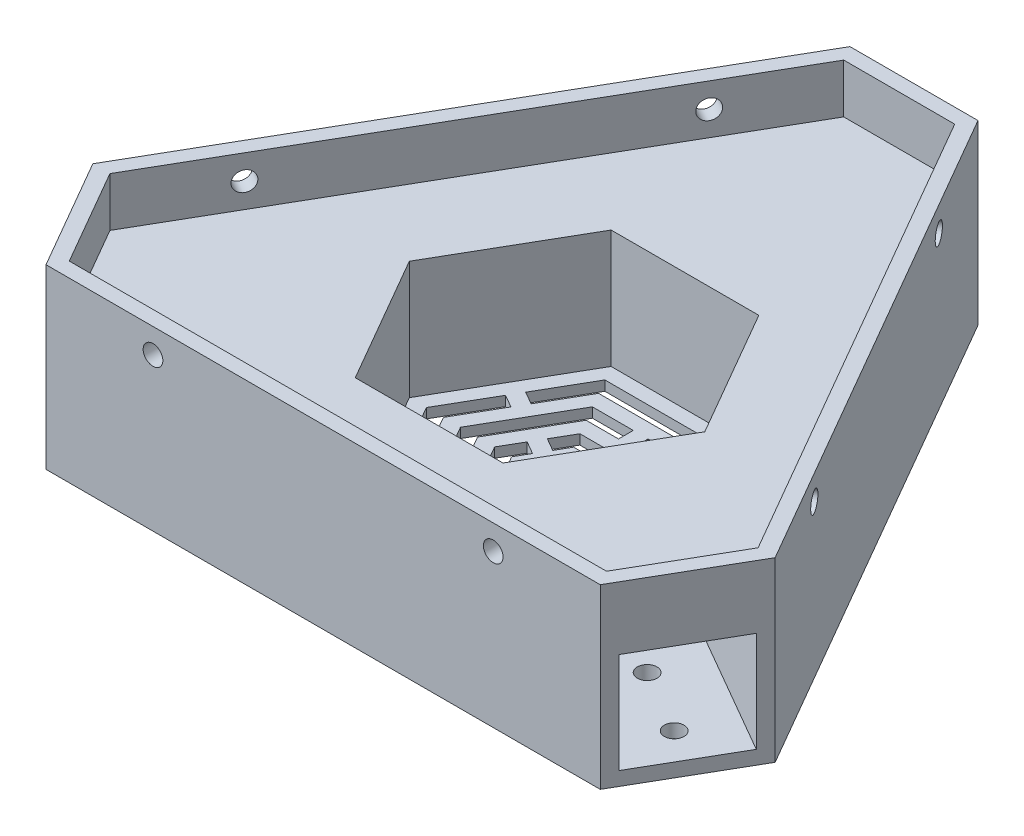
SolidWorks part; units mm, degrees
ref_plane "Front Plane" through (0, 0, 0) normal (0, 0, 1) x (1, 0, 0)
ref_plane "Top Plane" through (0, 0, 0) normal (0, 1, 0) x (1, 0, 0)
ref_plane "Right Plane" through (0, 0, 0) normal (1, 0, 0) x (0, 0, -1)
sketch "Sketch1" plane through (0, 0, 0) normal (0, 1, 0) x (1, 0, 0)
  line L0 (-11.2679, 69.4944) -> (11.2679, 69.4944)
  line L1 (15, 25.9808) -> (-15, 25.9808)
  line L2 (-15, 25.9808) -> (-30, 0)
  line L3 (-30, 0) -> (-15, -25.9808)
  line L4 (-15, -25.9808) -> (15, -25.9808)
  line L5 (15, -25.9808) -> (30, 0)
  line L6 (30, 0) -> (15, 25.9808)
  line L7 (-11.2679, 69.4944) -> (-38.5429, 22.2528)
  line L8 (11.2679, 69.4944) -> (38.5429, 22.2528)
  line L9 (41.141, 23.7528) -> (13, 72.4944)
  line L10 (13, 72.4944) -> (-13, 72.4944)
  line L11 (-13, 72.4944) -> (-41.141, 23.7528)
  line L12 (0, 0) -> (0, 113.4171) construction
  line L13 (0, 0) -> (-77.6761, 44.8463) construction
  line L14 (0, 0) -> (87.0373, 50.251) construction
  line L15 (69.282, -24.9889) -> (41.141, 23.7528)
  line L16 (65.8179, -24.9889) -> (38.5429, 22.2528)
  line L17 (56.282, -47.5056) -> (69.282, -24.9889)
  line L18 (65.8179, -24.9889) -> (54.55, -44.5056)
  line L19 (0, -47.5056) -> (56.282, -47.5056)
  line L20 (54.55, -44.5056) -> (0, -44.5056)
  line L21 (-56.282, -47.5056) -> (0, -47.5056)
  line L22 (-54.55, -44.5056) -> (0, -44.5056)
  line L23 (-69.282, -24.9889) -> (-56.282, -47.5056)
  line L24 (-54.55, -44.5056) -> (-65.8179, -24.9889)
  line L25 (-41.141, 23.7528) -> (-69.282, -24.9889)
  line L26 (-65.8179, -24.9889) -> (-38.5429, 22.2528)
  circle A0 centre (0, 0) radius 25.9808 construction
  point P15 (0, 69.4944)
  point P19 (0, 72.4944)
  point P41 (0, 0)
  dimension "D1" = 30
  dimension "D2" = 3
  dimension "D3" = 3
  dimension "D5" = 26
  dimension "D6" = 120
  dimension "D4" = 3
extrude "Boss-Extrude1" add sketch "Sketch1" along normal blind 2 contours L5 L6 L1 L2 L3 L4 region at (0, 0, 0)
extrude "Boss-Extrude2" add sketch "Sketch1<3>" along normal blind 26 contours L11 L25 L23 L21 L19 L17 L15 L9 L10 L24 L26 L7 L0 L8 L16 L18 L20 L22 | L26 L24 L22 L20 L18 L16 L8 L0 L7 L6 L5 L4 L3 L2 L1 region at (0, 0, -67.7531) region at (53.6241, 0, 1.5346)
sketch "Sketch1<3>" plane through (0, 0, 0) normal (0, 1, 0) x (1, 0, 0) same geometry as "Sketch1"
sketch "Sketch2" plane through (62.782, 0, 36.2472) normal (0.866, 0, 0.5) x (0.5, 0, -0.866)
  line L0 (-13, 26) -> (13, 0) construction
  line L1 (13, 26) -> (-13, 0) construction
  line L3 (-10.2, 2.8) -> (10.2, 2.8)
  line L4 (-10.2, 2.8) -> (-10.2, 23.2)
  line L5 (-10.2, 23.2) -> (10.2, 23.2)
  line L6 (10.2, 2.8) -> (10.2, 23.2)
  line L7 (-10.2, 2.8) -> (10.2, 23.2) construction
  line L8 (-10.2, 23.2) -> (10.2, 2.8) construction
  point P8 (0, 13)
  dimension "D1" = 20.4
extrude "Cut-Extrude1" cut sketch "Sketch2" against normal blind 30
ref_axis "Axis1" through (0, 27.3, 0) along (0, -1, 0)
pattern_circular "CirPattern1" count 3 over 360 about axis through (0, 27.3, 0) along (0, -1, 0) of "Cut-Extrude1"
sketch "Sketch3" plane through (0, 26, 0) normal (0, 1, 0) x (1, 0, 0)
  line L0 (-15, -25.9808) -> (15, -25.9808)
  line L1 (15, -25.9808) -> (30, 0)
  line L2 (30, 0) -> (15, 25.9808)
  line L3 (15, 25.9808) -> (-15, 25.9808)
  line L4 (-15, 25.9808) -> (-30, 0)
  line L5 (-30, 0) -> (-15, -25.9808)
  line L6 (0, -25.9808) -> (0, 25.9808) construction
  line L7 (1.5, 25.9808) -> (1.5, -25.9808) construction
  line L8 (-1.5, 25.9808) -> (-1.5, -25.9808) construction
  line L9 (23.25, -11.6913) -> (-21.75, 14.2894) construction
  line L10 (-22.5, 12.9904) -> (22.5, -12.9904) construction
  line L11 (21.75, -14.2894) -> (-23.25, 11.6913) construction
  line L12 (-21.75, -14.2894) -> (23.25, 11.6913) construction
  line L13 (22.5, 12.9904) -> (-22.5, -12.9904) construction
  line L14 (-23.25, -11.6913) -> (21.75, 14.2894) construction
  line L15 (30, 0) -> (15, 25.9808) construction
  line L16 (0, 22.9808) -> (13.2679, 22.9808)
  line L17 (13.2679, 22.9808) -> (19.1519, 12.7894)
  line L18 (19.1519, 12.7894) -> (16.5538, 11.2894)
  line L19 (16.5538, 11.2894) -> (11.5359, 19.9808)
  line L20 (11.5359, 19.9808) -> (0, 19.9808)
  line L21 (19.6077, 0) -> (9.8038, 16.9808)
  line L22 (9.8038, 16.9808) -> (1.5, 16.9808)
  line L23 (1.5, 16.9808) -> (1.5, 13.9808)
  line L24 (1.5, 13.9808) -> (8.0718, 13.9808)
  line L25 (8.0718, 13.9808) -> (16.1436, 0)
  line L26 (6.1615, 5.2894) -> (8.7596, 6.7894)
  line L27 (8.7596, 6.7894) -> (6.3397, 10.9808)
  line L28 (6.3397, 10.9808) -> (0, 10.9808)
  line L29 (8.7596, 6.7894) -> (10.2596, 4.1913)
  line L30 (6.1615, 5.2894) -> (7.6615, 2.6913)
  line L31 (6.1615, 5.2894) -> (4.6077, 7.9808)
  line L32 (4.6077, 7.9808) -> (1.5, 7.9808)
  line L33 (1.5, 7.9808) -> (0, 7.9808)
  line L34 (1.5, 7.9808) -> (1.5, 4.9808)
  line L35 (1.5, 4.9808) -> (2.8756, 4.9808)
  line L36 (2.8756, 4.9808) -> (5.7513, 0)
  line L37 (7.6615, -2.6913) -> (5.0635, -1.1913)
  line L38 (7.6615, 2.6913) -> (10.2596, 4.1913)
  line L39 (15.4558, -7.1913) -> (12.8577, -5.6913)
  line L40 (20.6519, 10.1913) -> (18.0538, 8.6913)
  line L41 (5.0635, -1.1913) -> (5.7513, 0)
  line L42 (7.6615, 2.6913) -> (9.2154, 0)
  line L43 (7.6615, -2.6913) -> (6.9115, -3.9904)
  line L44 (9.2154, 0) -> (7.6615, -2.6913)
  line L45 (10.2596, 4.1913) -> (12.6795, 0)
  line L46 (12.6795, 0) -> (9.5096, -5.4904)
  line L47 (12.8577, -5.6913) -> (16.1436, 0)
  line L48 (19.6077, 0) -> (15.4558, -7.1913)
  line L49 (18.0538, 8.6913) -> (23.0718, 0)
  line L50 (23.0718, 0) -> (17.3038, -9.9904)
  line L51 (26.5359, 0) -> (20.6519, 10.1913)
  line L52 (19.9019, -11.4904) -> (26.5359, 0)
  line L53 (19.9019, -11.4904) -> (13.2679, -22.9808)
  line L54 (13.2679, -22.9808) -> (1.5, -22.9808)
  line L55 (1.5, -22.9808) -> (1.5, -19.9808)
  line L56 (1.5, -19.9808) -> (11.5359, -19.9808)
  line L57 (11.5359, -19.9808) -> (17.3038, -9.9904)
  line L58 (-9.8038, -16.9808) -> (9.8038, -16.9808)
  line L59 (9.8038, -16.9808) -> (13.9558, -9.7894)
  line L60 (13.9558, -9.7894) -> (11.3577, -8.2894)
  line L61 (11.3577, -8.2894) -> (8.0718, -13.9808)
  line L62 (8.0718, -13.9808) -> (-8.0718, -13.9808)
  line L63 (1.5, -7.9808) -> (1.5, -10.9808)
  line L64 (1.5, -10.9808) -> (6.3397, -10.9808)
  line L65 (6.3397, -10.9808) -> (9.5096, -5.4904)
  line L66 (1.5, -10.9808) -> (-1.5, -10.9808)
  line L67 (1.5, -7.9808) -> (-1.5, -7.9808)
  line L68 (1.5, -7.9808) -> (4.6077, -7.9808)
  line L69 (4.6077, -7.9808) -> (6.1615, -5.2894)
  line L70 (6.1615, -5.2894) -> (6.9115, -3.9904)
  line L71 (6.1615, -5.2894) -> (3.5635, -3.7894)
  line L72 (3.5635, -3.7894) -> (2.8756, -4.9808)
  line L73 (2.8756, -4.9808) -> (-2.8756, -4.9808)
  line L74 (-6.1615, -5.2894) -> (-3.5635, -3.7894)
  line L75 (-1.5, -7.9808) -> (-1.5, -10.9808)
  line L76 (-13.9558, -9.7894) -> (-11.3577, -8.2894)
  line L77 (-1.5, -22.9808) -> (-1.5, -19.9808)
  line L78 (-3.5635, -3.7894) -> (-2.8756, -4.9808)
  line L79 (-1.5, -7.9808) -> (-4.6077, -7.9808)
  line L80 (-6.1615, -5.2894) -> (-6.9115, -3.9904)
  line L81 (-4.6077, -7.9808) -> (-6.1615, -5.2894)
  line L82 (-1.5, -10.9808) -> (-6.3397, -10.9808)
  line L83 (-6.3397, -10.9808) -> (-9.5096, -5.4904)
  line L84 (-11.3577, -8.2894) -> (-8.0718, -13.9808)
  line L85 (-9.8038, -16.9808) -> (-13.9558, -9.7894)
  line L86 (-1.5, -19.9808) -> (-11.5359, -19.9808)
  line L87 (-11.5359, -19.9808) -> (-17.3038, -9.9904)
  line L88 (-13.2679, -22.9808) -> (-1.5, -22.9808)
  line L89 (-19.9019, -11.4904) -> (-13.2679, -22.9808)
  line L90 (-19.9019, -11.4904) -> (-26.5359, 0)
  line L91 (-26.5359, 0) -> (-20.6519, 10.1913)
  line L92 (-20.6519, 10.1913) -> (-18.0538, 8.6913)
  line L93 (-18.0538, 8.6913) -> (-23.0718, 0)
  line L94 (-23.0718, 0) -> (-17.3038, -9.9904)
  line L95 (-9.8038, 16.9808) -> (-19.6077, 0)
  line L96 (-19.6077, 0) -> (-15.4558, -7.1913)
  line L97 (-15.4558, -7.1913) -> (-12.8577, -5.6913)
  line L98 (-12.8577, -5.6913) -> (-16.1436, 0)
  line L99 (-16.1436, 0) -> (-8.0718, 13.9808)
  line L100 (-7.6615, 2.6913) -> (-10.2596, 4.1913)
  line L101 (-10.2596, 4.1913) -> (-12.6795, 0)
  line L102 (-12.6795, 0) -> (-9.5096, -5.4904)
  line L103 (-10.2596, 4.1913) -> (-8.7596, 6.7894)
  line L104 (-7.6615, 2.6913) -> (-6.1615, 5.2894)
  line L105 (-7.6615, 2.6913) -> (-9.2154, 0)
  line L106 (-9.2154, 0) -> (-7.6615, -2.6913)
  line L107 (-7.6615, -2.6913) -> (-6.9115, -3.9904)
  line L108 (-7.6615, -2.6913) -> (-5.0635, -1.1913)
  line L109 (-5.0635, -1.1913) -> (-5.7513, 0)
  line L110 (-5.7513, 0) -> (-2.8756, 4.9808)
  line L111 (-1.5, 7.9808) -> (-1.5, 4.9808)
  line L112 (-6.1615, 5.2894) -> (-8.7596, 6.7894)
  line L113 (-1.5, 16.9808) -> (-1.5, 13.9808)
  line L114 (-19.1519, 12.7894) -> (-16.5538, 11.2894)
  line L115 (-1.5, 4.9808) -> (-2.8756, 4.9808)
  line L116 (-6.1615, 5.2894) -> (-4.6077, 7.9808)
  line L117 (-1.5, 7.9808) -> (0, 7.9808)
  line L118 (-4.6077, 7.9808) -> (-1.5, 7.9808)
  line L119 (-8.7596, 6.7894) -> (-6.3397, 10.9808)
  line L120 (-6.3397, 10.9808) -> (0, 10.9808)
  line L121 (-1.5, 13.9808) -> (-8.0718, 13.9808)
  line L122 (-9.8038, 16.9808) -> (-1.5, 16.9808)
  line L123 (-16.5538, 11.2894) -> (-11.5359, 19.9808)
  line L124 (-11.5359, 19.9808) -> (0, 19.9808)
  line L125 (-13.2679, 22.9808) -> (-19.1519, 12.7894)
  line L126 (0, 22.9808) -> (-13.2679, 22.9808)
  line L127 (-1.5, 4.9808) -> (1.5, 4.9808)
  line L128 (5.0635, -1.1913) -> (3.5635, -3.7894)
  line L129 (-5.0635, -1.1913) -> (-3.5635, -3.7894)
  line L130 (15, 25.9808) -> (0, 0) construction
  point P34 (0, 0)
  point P58 (6.9115, 3.9904)
  point P66 (4.3135, 2.4904)
  point P68 (9.5096, 5.4904)
  point P71 (12.1077, 6.9904)
  point P72 (14.7058, 8.4904)
  point P104 (0, -7.9808)
  point P112 (0, -4.9808)
  point P114 (0, -10.9808)
  point P117 (0, -13.9808)
  point P118 (0, -16.9808)
  point P147 (-6.9115, 3.9904)
  point P155 (-4.3135, 2.4904)
  point P157 (-9.5096, 5.4904)
  point P160 (-12.1077, 6.9904)
  point P161 (-14.7058, 8.4904)
  point P165 (0, 0)
  dimension "D1" = 3
  dimension "D4" = 3
  dimension "D5" = 6
  dimension "D6" = 9
  dimension "D7" = 12
  dimension "D8" = 15
  dimension "D9" = 18
  dimension "D10" = 3
  dimension "D2" = 3
  dimension "D3" = 3
extrude "Cut-Extrude2" cut sketch "Sketch3" against normal through all contours L109 L129 L78 L73 L72 L128 L41 L36 L35 L127 L115 L110 | L70 L69 L68 L63 L64 L65 L46 L45 L38 L42 L44 L43 | L120 L119 L112 L116 L118 L117 L33 L32 L31 L26 L27 L28 | L107 L106 L105 L100 L101 L102 L83 L82 L75 L79 L81 L80 | L85 L58 L59 L60 L61 L62 L84 L76 | L48 L21 L22 L23 L24 L25 L47 L39 | L122 L95 L96 L97 L98 L99 L121 L113 | L16 L126 L125 L114 L123 L124 L20 L19 L18 L17 | L94 L93 L92 L91 L90 L89 L88 L77 L86 L87 | L57 L56 L55 L54 L53 L52 L51 L40 L49 L50 region at (6.634, 26, -22.5803) region at (12.18, 26, -7.0321) region at (0, 26, -8.8372) region at (7.6533, 26, 4.4186) region at (0, 26, 0) region at (-7.6533, 26, 4.4186) region at (23.234, 26, -4.8879) region at (0, 26, 14.0642) region at (-7.384, 26, 22.5652) region at (-12.18, 26, -7.0321)
sketch "Sketch4" plane through (0, 0, 0) normal (0, -1, 0) x (1, 0, 0)
  line L0 (0, -72.4944) -> (0, 0) construction
  line L1 (13, -72.4944) -> (-13, -72.4944) construction
  line L2 (-62.782, 36.2472) -> (0, 0) construction
  line L3 (62.782, 36.2472) -> (0, 0) construction
  circle A0 centre (0, -64.9944) radius 2
  circle A1 centre (0, -49.9944) radius 2
  circle A2 centre (-56.2868, 32.4972) radius 2
  circle A3 centre (-43.2965, 24.9972) radius 2
  circle A4 centre (56.2868, 32.4972) radius 2
  circle A5 centre (43.2965, 24.9972) radius 2
  point P21 (0, 0)
  dimension "D3" = 4
  dimension "D1" = 7.5
  dimension "D2" = 15
  dimension "D4" = 3
extrude "Cut-Extrude3" cut sketch "Sketch4" against normal blind 10
extrude "Boss-Extrude4" add sketch "Sketch1<5>" along normal blind 10 from surface contours L11 L25 L23 L21 L19 L17 L15 L9 L10 L24 L26 L7 L0 L8 L16 L18 L20 L22 region at (53.6241, 0, 1.5346) starting at face at (0, 26, 0)
sketch "Sketch1<5>" plane through (0, 0, 0) normal (0, 1, 0) x (1, 0, 0) same geometry as "Sketch1"
sketch "Sketch5" plane through (-38.5429, 0, -22.2528) normal (0.866, 0, 0.5) x (0.5, 0, -0.866)
  line L0 (-54.55, 31) -> (54.55, 31) construction
  line L1 (-54.55, 36) -> (-54.55, 26) construction
  line L2 (54.55, 36) -> (54.55, 26) construction
  line L3 (0, 36) -> (0, 26) construction
  line L4 (54.55, 36) -> (-54.55, 36) construction
  line L5 (54.55, 26) -> (-54.55, 26) construction
  circle A0 centre (-34.55, 31) radius 2
  circle A1 centre (34.55, 31) radius 2
  dimension "D2" = 4
  dimension "D1" = 20
extrude "Cut-Extrude4" cut sketch "Sketch5" against normal blind 10
pattern_circular "CirPattern2" count 3 over 360 about axis through (0, 27.3, 0) along (0, -1, 0) of "Cut-Extrude4"
